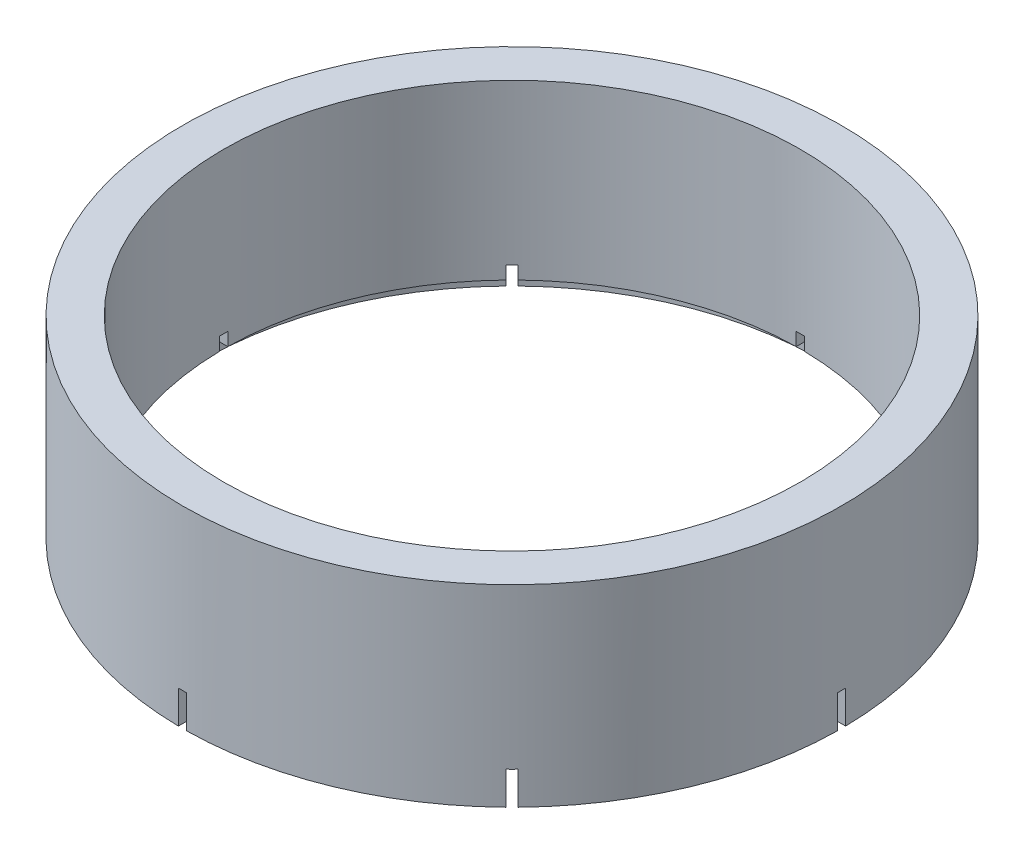
SolidWorks part; units mm, degrees
material "C (Graphite)"
ref_plane "Front Plane" through (0, 0, 0) normal (0, 0, 1) x (1, 0, 0)
ref_plane "Top Plane" through (0, 0, 0) normal (0, 1, 0) x (1, 0, 0)
ref_plane "Right Plane" through (0, 0, 0) normal (1, 0, 0) x (0, 0, -1)
sketch "Sketch1" plane through (0, 0, 0) normal (0, 1, 0) x (1, 0, 0)
  circle A0 centre (0, 0) radius 40
  circle A1 centre (0, 0) radius 35
  dimension "D1" = 80
  dimension "D2" = 70
extrude "Boss-Extrude1" add sketch "Sketch1" along normal blind 25.4
sketch "Sketch2" plane through (0, 0, 0) normal (0, -1, 0) x (1, 0, 0)
  circle A0 centre (0, 0) radius 37.5
  circle A1 centre (0, 0) radius 35
  dimension "D1" = 75
  dimension "D2" = 70
extrude "Cut-Extrude1" cut sketch "Sketch2" against normal blind 4.4
sketch "Sketch3" plane through (0, 0, 0) normal (0, 0, 1) x (1, 0, 0)
  line L0 (44, 0) -> (-44, 0) construction
  line L1 (-0.5, 0) -> (0.5, 0)
  line L2 (-0.5, 0) -> (-0.5, 6)
  line L3 (-0.5, 6) -> (0.5, 6)
  line L4 (0.5, 0) -> (0.5, 6)
  line L5 (0, -13.97) -> (0, 13.97) construction
  point P6 (0, 6)
  dimension "D1" = 0
  dimension "D2" = 1
  dimension "D3" = 6
extrude "Cut-Extrude2" cut sketch "Sketch3" against normal through all both and the other way through all
pattern_circular "CirPattern1" count 4 every 45 about axis through (0, 25.4, 0) along (0, -1, 0) of "Cut-Extrude2" reverse direction yes
sketch "Sketch4" plane through (0, 0, 0) normal (0, -1, 0) x (1, 0, 0)
  circle A0 centre (0, 0) radius 45.8776
extrude "Cut-Extrude3" cut sketch "Sketch4" against normal blind 2
